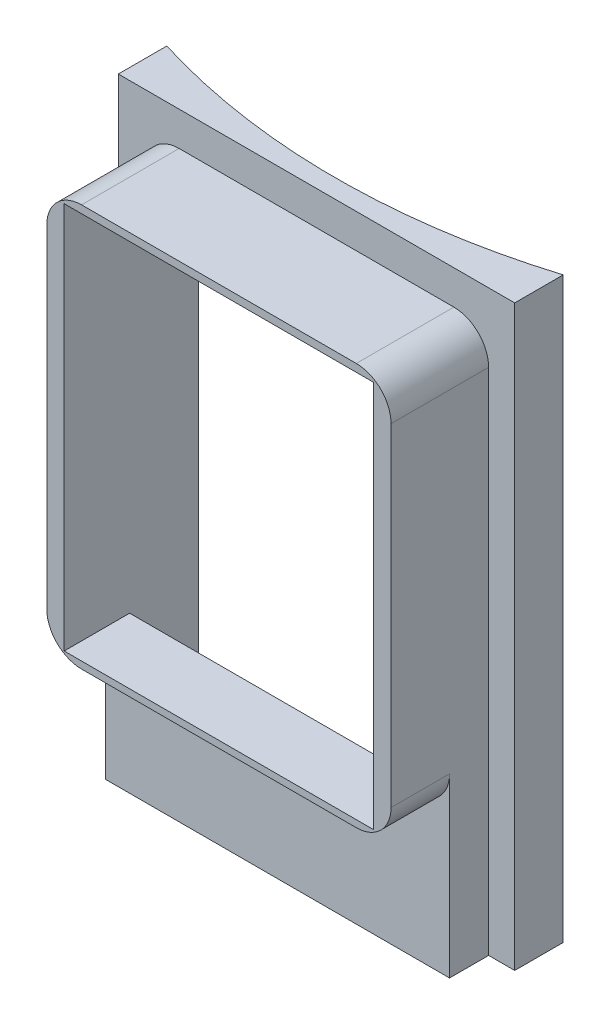
SolidWorks part; units mm, degrees
ref_plane "Front Plane" through (0, 0, 0) normal (0, 0, 1) x (1, 0, 0)
ref_plane "Top Plane" through (0, 0, 0) normal (0, 1, 0) x (1, 0, 0)
ref_plane "Right Plane" through (0, 0, 0) normal (1, 0, 0) x (0, 0, -1)
sketch "Sketch1" plane through (0, 0, 0) normal (0, 0, 1) x (1, 0, 0)
  line L1 (-46.99, 86.36) -> (97.79, 86.36)
  line L2 (-46.99, 86.36) -> (-46.99, -124.798)
  line L3 (-46.99, -124.798) -> (97.79, -124.798)
  line L4 (97.79, 86.36) -> (97.79, -124.798)
  dimension "D1" = 144.78
  dimension "D2" = 211.158
extrude "Extrude1" add sketch "Sketch1" along normal blind 252.4252
sketch "Sketch2" plane through (0, 86.36, 0) normal (0, 1, 0) x (-1, 0, 0)
  line L0 (-97.79, 0) -> (46.99, 0) construction
  circle A1 centre (-25.4, 0) radius 245.618
sketch "Sketch7" plane through (0, 0, 252.4252) normal (0, 0, 1) x (1, 0, 0)
  line L0 (-46.99, 86.36) -> (-46.99, -124.798) construction
  line L1 (-37.465, 73.915) -> (88.265, 73.915)
  line L2 (-37.465, 73.915) -> (-37.465, -124.798)
  line L3 (-37.465, -124.798) -> (88.265, -124.798)
  line L4 (88.265, 73.915) -> (88.265, -124.798)
  line L5 (97.79, -124.798) -> (97.79, 86.36) construction
  line L6 (97.79, 86.36) -> (-46.99, 86.36) construction
  line L7 (-46.99, -124.798) -> (97.79, -124.798) construction
  point P8 (25.4, 73.915)
  point P9 (0, 0)
  dimension "D1" = 9.525
  dimension "D2" = 9.525
  dimension "D3" = 12.445
extrude "Extrude5" add sketch "Sketch7" along normal blind 35.6442
sketch "Sketch4" plane through (0, 0, 252.4252) normal (0, 0, 1) x (1, 0, 0)
  line L0 (97.79, 86.36) -> (-46.99, 86.36) construction
  line L1 (-31.115, 71.104) -> (81.915, 71.104)
  line L2 (-31.115, 71.104) -> (-31.115, -70.376)
  line L3 (-31.115, -70.376) -> (81.915, -70.376)
  line L4 (81.915, 71.104) -> (81.915, -70.376)
  line L5 (88.265, 73.915) -> (-37.465, 73.915) construction
  line L6 (88.265, 73.915) -> (-37.465, 73.915) construction
  point P4 (25.4, 71.104)
  point P5 (25.4, 86.36)
  point P6 (25.4, 73.915)
  dimension "D1" = 2.811
  dimension "D2" = 141.48
extrude "Extrude2" cut sketch "Sketch4" against normal blind 273.8502 and the other way blind 42.08
sketch "Sketch10" plane through (0, 0, 0) normal (0, 0, -1) x (-1, 0, 0)
  line L0 (46.99, -124.798) -> (-97.79, -124.798) construction
  line L1 (-81.915, 71.104) -> (31.115, 71.104)
  line L2 (-81.915, 71.104) -> (-81.915, 71.1041)
  line L3 (-81.915, 71.1041) -> (31.115, 71.1041)
  line L4 (31.115, 71.104) -> (31.115, 71.1041)
  line L5 (-81.915, -70.376) -> (31.115, -70.376)
  line L6 (-81.915, -70.376) -> (-81.915, -122.258)
  line L7 (-81.915, -122.258) -> (31.115, -122.258)
  line L8 (31.115, -70.376) -> (31.115, -122.258)
  dimension "D1" = 2.54
  dimension "D2" = 0.0001
extrude "Extrude8" cut sketch "Sketch10" against normal blind 264.16
extrude "Extrude4" cut sketch "Sketch2" against normal blind 230
sketch "Sketch12" plane through (0, 0, 288.0694) normal (0, 0, 1) x (1, 0, 0)
  line L0 (88.265, -124.798) -> (88.265, 73.915) construction
  line L1 (-37.465, -124.798) -> (88.265, -124.798)
  line L2 (-37.465, -124.798) -> (-37.465, -72.917)
  line L3 (-37.465, -72.917) -> (88.265, -72.917)
  line L4 (88.265, -124.798) -> (88.265, -72.917)
extrude "Extrude10" cut sketch "Sketch12" against normal blind 21.3694 contours L2 L3 L4 L1
fillet "Fillet3" radius 12.7 4 edges at (-37.465, -72.917, 277.3847) (88.265, -72.917, 277.3847) (88.265, 73.915, 270.2473) (-37.465, 73.915, 270.2473)
